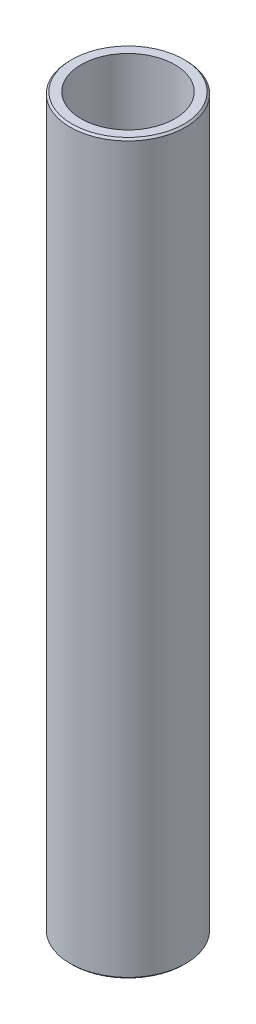
SolidWorks part; units mm, degrees
ref_plane "Front Plane" through (0, 0, 0) normal (0, 0, 1) x (1, 0, 0)
ref_plane "Top Plane" through (0, 0, 0) normal (0, 1, 0) x (1, 0, 0)
ref_plane "Right Plane" through (0, 0, 0) normal (1, 0, 0) x (0, 0, -1)
sketch "Sketch1" plane through (0, 0, 0) normal (0, 1, 0) x (1, 0, 0)
  circle A0 centre (0, 0) radius 7.94
  circle A1 centre (0, 0) radius 6.44
  dimension "D1" = 15.88
  dimension "D2" = 1.5
extrude "Boss-Extrude1" add sketch "Sketch1" along normal blind 100
chamfer "Chamfer1" distance 0.25 angle 45 2 edges at (0, 0, 7.94) (0, 100, 7.94)
